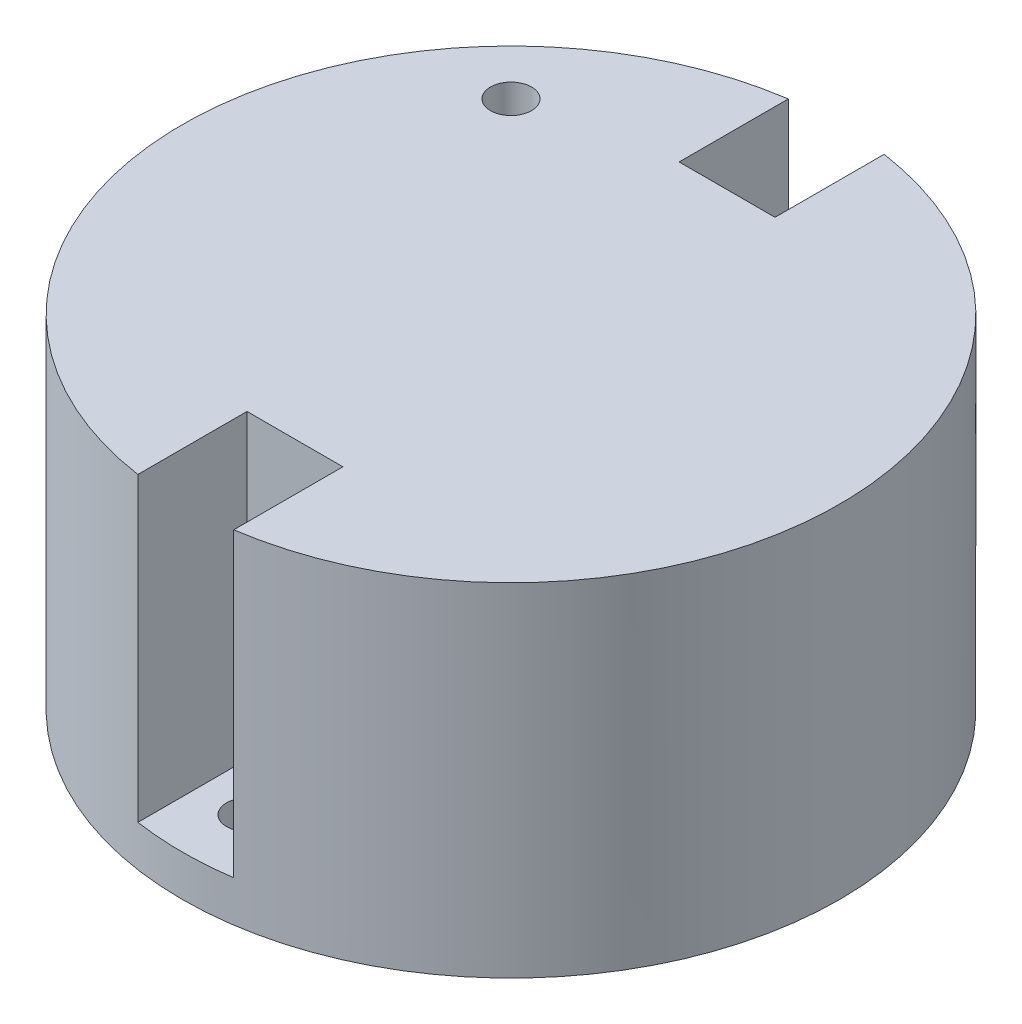
SolidWorks part; units mm, degrees
ref_plane "Front Plane" through (0, 0, 0) normal (0, 0, 1) x (1, 0, 0)
ref_plane "Top Plane" through (0, 0, 0) normal (0, 1, 0) x (1, 0, 0)
ref_plane "Right Plane" through (0, 0, 0) normal (1, 0, 0) x (0, 0, -1)
sketch "Sketch1" plane through (0, 0, 0) normal (0, 1, 0) x (1, 0, 0)
  line L0 (-3.5, 22.775) -> (-3.5, 15.775)
  line L1 (-3.5, 15.775) -> (3.5, 15.775)
  line L2 (3.5, 15.775) -> (3.5, 22.775)
  line L3 (-3.5, -22.775) -> (-3.5, -15.775)
  line L4 (-3.5, -15.775) -> (3.5, -15.775)
  line L5 (3.5, -15.775) -> (3.5, -22.775)
  circle A0 centre (0, 0) radius 24
  circle A1 centre (0, 0) radius 14.55
  circle A2 centre (0, 19.275) radius 1.5
  circle A3 centre (0, -19.275) radius 1.5
  arc A4 (-3.5, 22.775) -> (-3.5, -22.775) centre (0, 0) ccw
  arc A5 (3.5, -22.775) -> (3.5, 22.775) centre (0, 0) ccw
  dimension "D1" = 48
  dimension "D2" = 29.1
  dimension "D3" = 3
  dimension "D4" = 3
  dimension "D5" = 19.275
  dimension "D6" = 19.275
  dimension "D7" = 3.5
  dimension "D8" = 3.5
  dimension "D9" = 22.775
  dimension "D10" = 3.5
  dimension "D11" = 3.5
  dimension "D12" = 22.775
  dimension "D13" = 3.5
  dimension "D14" = 0
  dimension "D15" = 3.5
extrude "Boss-Extrude2" add sketch "Sketch1" along normal blind 25 contours A0
sketch "Sketch3" plane through (0, 25, 0) normal (0, 1, 0) x (1, 0, 0)
  line L0 (-3.5, 15.775) -> (-3.5, 23.7434)
  line L1 (-3.5, 15.775) -> (3.5, 15.775)
  line L2 (3.5, 15.775) -> (3.5, 23.7434)
  line L3 (-3.5, -15.775) -> (-3.5, -23.7434)
  line L4 (-3.5, -15.775) -> (3.5, -15.775)
  line L5 (3.5, -15.775) -> (3.5, -23.3424)
  line L6 (3.5, -23.7434) -> (3.5, -23.3424)
  circle A0 centre (0, 19.275) radius 1.5
  circle A1 centre (0, -19.275) radius 1.5
  circle A2 centre (0, 0) radius 24
  circle M9 centre (0, 0) radius 24
  dimension "D5" = 19.275
  dimension "D8" = 3.5
  dimension "D10" = 3.5
  dimension "D11" = 3.5
  dimension "D1" = 3
  dimension "D2" = 3
  dimension "D13" = 48
  dimension "D4" = 19.275
  dimension "D6" = 3.5
  dimension "D9" = 3.5
  dimension "D12" = 3.5
extrude "Cut-Extrude2" cut sketch "Sketch3" against normal blind 22 contours L1 L2 L0 A0 M9 | L6 L5 L4 L3 A1 M9 region at (-3.392, 25, -19.7592) region at (-3.392, 25, 19.7592)
sketch "Sketch7" plane through (0, 25, 0) normal (0, 1, 0) x (1, 0, 0)
  circle A0 centre (0, -19.275) radius 1.5
extrude "Cut-Extrude3" cut sketch "Sketch7" against normal blind 30
sketch "Sketch8" plane through (0, 25, 0) normal (0, 1, 0) x (1, 0, 0)
  circle A0 centre (0, 19.275) radius 1.5
extrude "Cut-Extrude4" cut sketch "Sketch8" against normal blind 30
sketch "Sketch9" plane through (0, 0, 0) normal (0, -1, 0) x (1, 0, 0)
  line L0 (-5.5, 22.275) -> (-5.5, 13.775)
  line L1 (-5.5, 13.775) -> (5.5, 13.775)
  line L2 (5.5, 13.775) -> (5.5, 22.275)
  line L3 (-5.5, -22.275) -> (-5.5, -13.775)
  line L4 (-5.5, -13.775) -> (5.5, -13.775)
  line L5 (5.5, -13.775) -> (5.5, -22.275)
  arc A0 (-5.5, -22.275) -> (-5.5, 22.275) centre (0, 0) cw
  arc A1 (5.5, -22.275) -> (5.5, 22.275) centre (0, 0) ccw
  circle A2 centre (0, 19.275) radius 1.5
  circle A3 centre (0, -19.275) radius 1.5
  dimension "D1" = 5.5
  dimension "D2" = 5.5
  dimension "D3" = 5.5
  dimension "D4" = 5.5
  dimension "D5" = 22.275
  dimension "D6" = 22.275
  dimension "D7" = 5.5
  dimension "D8" = 5.5
extrude "Cut-Extrude6" cut sketch "Sketch9" against normal blind 20
sketch "Sketch10" plane through (0, 20, 0) normal (0, -1, 0) x (1, 0, 0)
  line L0 (0, 13.775) -> (0, -13.775)
  line L1 (5.5, 13.775) -> (-5.5, 13.775) construction
  line L2 (-5.5, -13.775) -> (5.5, -13.775) construction
fillet "Fillet11" radius 10 2 edges at (0, 20, -13.775) (0, 20, 13.775)
fillet "Fillet13" radius 17 1 edges at (-22.944, 20, 0)
fillet "Fillet14" radius 17 1 edges at (22.944, 20, 0)
fillet "Fillet16" radius 3 2 edges at (5.5, 5, 13.775) (5.5, 16.688, 11.2094)
fillet "Fillet17" radius 3 2 edges at (-5.5, 5, 13.775) (-5.5, 16.688, 11.2094)
fillet "Fillet18" radius 3 4 edges at (-5.5, 5, -13.775) (5.5, 5, -13.775) (-5.5, 16.688, -11.2094) (5.5, 16.688, -11.2094)
sketch "Sketch11" plane through (0, 25, 0) normal (0, 1, 0) x (1, 0, 0)
  line L0 (0, 0) -> (-24, 0)
  line L1 (0, 0) -> (-13.6295, 13.6295)
  arc A0 (-3.5, 23.7434) -> (-3.5, -23.7434) centre (0, 0) ccw construction
  circle A1 centre (-13.6295, 13.6295) radius 1.5
  dimension "D3" = 3
  dimension "D1" = 19.275
  dimension "D2" = 45
extrude "Cut-Extrude7" cut sketch "Sketch11" against normal blind 30 contours A1 region at (-12.2829, 25, -13.0717)
equation "\"TubeInnerDiameter\"= 48mm"
equation "\"MotorCasingDiameter\"= 29.1mm"
equation "\"BoltDiameter\"= 5mm"
equation "\"DomeHeight\"= 25mm"
equation "\"TopBoltDiameter\"= 3mm"
equation "\"PressureChannelWidth\"= 8mm"
equation "\"IgniterChannelWidth\"= 2.8mm"
equation "\"BoltChannelSeparation\"= 2mm"
equation "\"PressureChannelChamferRadius\"= 3mm"
equation "\"D1@Sketch1\"=\"TubeInnerDiameter\""
equation "\"D2@Sketch1\"=\"MotorCasingDiameter\""
equation "\"D3@Sketch1\"=\"TopBoltDiameter\""
equation "\"D4@Sketch1\"=\"TopBoltDiameter\""
equation "\"D5@Sketch1\"=(\"TubeInnerDiameter\"/2+\"MotorCasingDiameter\"/2)/2"
equation "\"D6@Sketch1\"=(\"TubeInnerDiameter\"/2+\"MotorCasingDiameter\"/2)/2"
equation "\"D7@Sketch1\"=\"TopBoltDiameter\"/2+\"BoltChannelSeparation\""
equation "\"D8@Sketch1\"=\"TopBoltDiameter\"/2+\"BoltChannelSeparation\""
equation "\"D9@Sketch1\"=(\"TubeInnerDiameter\"/2+\"MotorCasingDiameter\"/2)/2+\"PressureChannelWidth\"/2-0.5"
equation "\"D10@Sketch1\"=\"TopBoltDiameter\"/2+\"BoltChannelSeparation\""
equation "\"D11@Sketch1\"=\"TopBoltDiameter\"/2+\"BoltChannelSeparation\""
equation "\"D12@Sketch1\"=(\"TubeInnerDiameter\"/2+\"MotorCasingDiameter\"/2)/2+(\"PressureChannelWidth\"/2)-0.5"
equation "\"D13@Sketch1\"=\"TopBoltDiameter\"/2+\"BoltChannelSeparation\""
equation "\"D15@Sketch1\"=\"TopBoltDiameter\"/2+\"BoltChannelSeparation\""
equation "\"D1@Boss-Extrude2\"=\"DomeHeight\""
equation "\"D1@Sketch3\"=\"TopBoltDiameter\""
equation "\"D2@Sketch3\"=\"TopBoltDiameter\""
equation "\"D4@Sketch3\"=(\"TubeInnerDiameter\"/2+\"MotorCasingDiameter\"/2)/2"
equation "\"D5@Sketch3\"=(\"TubeInnerDiameter\"/2+\"MotorCasingDiameter\"/2)/2"
equation "\"D6@Sketch3\"=\"TopBoltDiameter\"/2+\"BoltChannelSeparation\""
equation "\"D8@Sketch3\"=\"TopBoltDiameter\"/2+\"BoltChannelSeparation\""
equation "\"D9@Sketch3\"=\"TopBoltDiameter\"/2+\"BoltChannelSeparation\""
equation "\"D10@Sketch3\"=\"TopBoltDiameter\"/2+\"BoltChannelSeparation\""
equation "\"D11@Sketch3\"=\"TopBoltDiameter\"/2+\"BoltChannelSeparation\""
equation "\"D12@Sketch3\"=\"TopBoltDiameter\"/2+\"BoltChannelSeparation\""
equation "\"D13@Sketch3\"=\"TubeInnerDiameter\""
equation "\"D1@Sketch9\"=2mm+\"TopBoltDiameter\"/2+\"BoltChannelSeparation\""
equation "\"D2@Sketch9\"=\"TopBoltDiameter\"/2+\"BoltChannelSeparation\"+2mm"
equation "\"D3@Sketch9\"=2mm+\"TopBoltDiameter\"/2+\"BoltChannelSeparation\""
equation "\"D4@Sketch9\"=\"TopBoltDiameter\"/2+\"BoltChannelSeparation\"+2mm"
equation "\"D5@Sketch9\"=(\"TubeInnerDiameter\"/2+\"MotorCasingDiameter\"/2)/2+\"PressureChannelWidth\"/2-01"
equation "\"D6@Sketch9\"=(\"TubeInnerDiameter\"/2+\"MotorCasingDiameter\"/2)/2+\"PressureChannelWidth\"/2-1"
equation "\"D7@Sketch9\"=2mm+\"TopBoltDiameter\"/2+\"BoltChannelSeparation\""
equation "\"D8@Sketch9\"=\"TopBoltDiameter\"/2+\"BoltChannelSeparation\"+2mm"
equation "\"D1@Sketch11\"=(\"TubeInnerDiameter\"/2+\"MotorCasingDiameter\"/2)/2"
